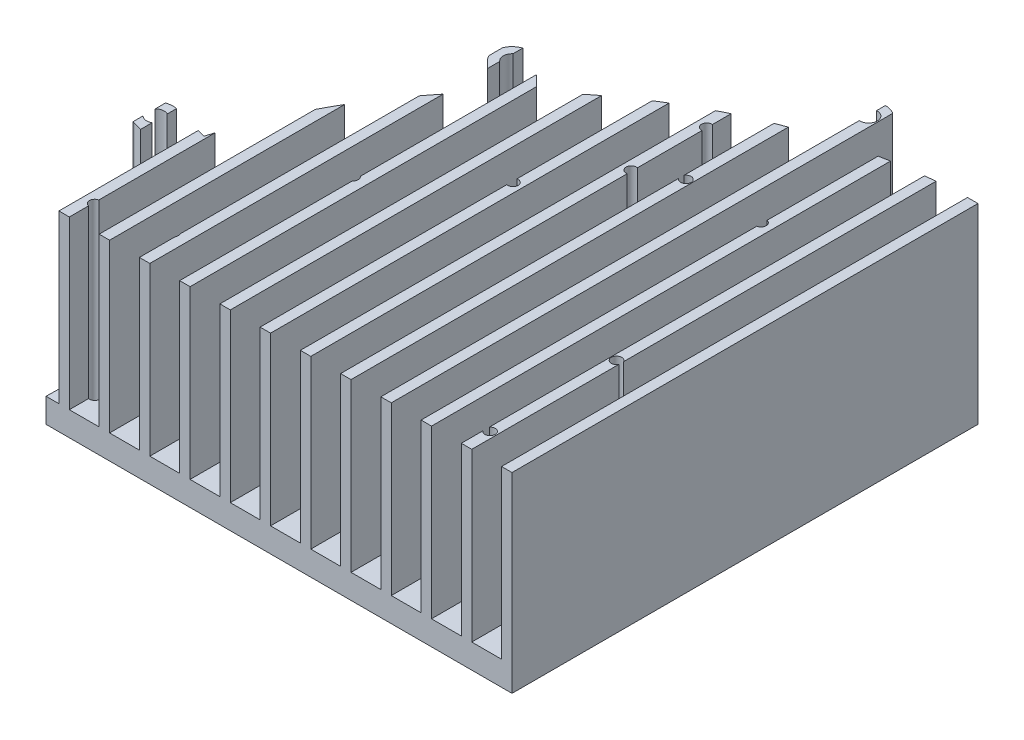
SolidWorks part; units mm, degrees
ref_plane "Ön Düzlem" through (0, 0, 0) normal (0, 0, 1) x (1, 0, 0)
ref_plane "Üst Düzlem" through (0, 0, 0) normal (0, 1, 0) x (1, 0, 0)
ref_plane "Sağ Düzlem" through (0, 0, 0) normal (1, 0, 0) x (0, 0, -1)
sketch "Sketch1" plane through (0, 0, 0) normal (0, 0, 1) x (1, 0, 0)
  line L0 (11.5714, 7) -> (11.5714, 55)
  line L1 (0, 0) -> (165, 0)
  line L2 (0, 0) -> (0, 7)
  line L3 (3, 7) -> (11.5714, 7)
  line L4 (165, 0) -> (165, 10)
  line L6 (0, 7) -> (0, 55)
  line L7 (0, 55) -> (3, 55)
  line L8 (3, 7) -> (3, 55)
  line L10 (14.5714, 7) -> (14.5714, 55)
  line L11 (11.5714, 55) -> (14.5714, 55)
  line L12 (23.1429, 7) -> (23.1429, 55)
  line L14 (26.1429, 7) -> (26.1429, 55)
  line L15 (23.1429, 55) -> (26.1429, 55)
  line L16 (34.7143, 7) -> (34.7143, 55)
  line L18 (37.7143, 7) -> (37.7143, 55)
  line L19 (34.7143, 55) -> (37.7143, 55)
  line L20 (46.2857, 7) -> (46.2857, 55)
  line L22 (49.2857, 7) -> (49.2857, 55)
  line L23 (46.2857, 55) -> (49.2857, 55)
  line L24 (57.8571, 7) -> (57.8571, 55)
  line L26 (60.8571, 7) -> (60.8571, 55)
  line L27 (57.8571, 55) -> (60.8571, 55)
  line L28 (69.4286, 7) -> (69.4286, 55)
  line L30 (72.4286, 7) -> (72.4286, 55)
  line L31 (69.4286, 55) -> (72.4286, 55)
  line L32 (81, 7) -> (81, 55)
  line L34 (84, 7) -> (84, 55)
  line L35 (81, 55) -> (84, 55)
  line L36 (92.5714, 7) -> (92.5714, 55)
  line L38 (95.5714, 7) -> (95.5714, 55)
  line L39 (92.5714, 55) -> (95.5714, 55)
  line L40 (104.1429, 7) -> (104.1429, 55)
  line L42 (107.1429, 7) -> (107.1429, 55)
  line L43 (104.1429, 55) -> (107.1429, 55)
  line L44 (115.7143, 7) -> (115.7143, 55)
  line L46 (118.7143, 7) -> (118.7143, 55)
  line L47 (115.7143, 55) -> (118.7143, 55)
  line L48 (127.2857, 7) -> (127.2857, 55)
  line L50 (130.2857, 7) -> (130.2857, 55)
  line L51 (127.2857, 55) -> (130.2857, 55)
  line L52 (138.8571, 7) -> (138.8571, 55)
  line L54 (141.8571, 7) -> (141.8571, 55)
  line L55 (138.8571, 55) -> (141.8571, 55)
  line L56 (150.4286, 7) -> (150.4286, 55)
  line L58 (153.4286, 7) -> (153.4286, 55)
  line L59 (150.4286, 55) -> (153.4286, 55)
  line L60 (162, 7) -> (162, 55)
  line L62 (165, 7) -> (165, 55)
  line L63 (162, 55) -> (165, 55)
  line L78 (14.5714, 7) -> (23.1429, 7)
  line L79 (26.1429, 7) -> (34.7143, 7)
  line L80 (37.7143, 7) -> (46.2857, 7)
  line L81 (49.2857, 7) -> (57.8571, 7)
  line L82 (60.8571, 7) -> (69.4286, 7)
  line L83 (72.4286, 7) -> (81, 7)
  line L84 (84, 7) -> (92.5714, 7)
  line L85 (95.5714, 7) -> (104.1429, 7)
  line L86 (107.1429, 7) -> (115.7143, 7)
  line L87 (118.7143, 7) -> (127.2857, 7)
  line L88 (130.2857, 7) -> (138.8571, 7)
  line L89 (141.8571, 7) -> (150.4286, 7)
  line L90 (153.4286, 7) -> (162, 7)
  dimension "D1" = 165
  dimension "D2" = 7
  dimension "D3" = 48
  dimension "D4" = 3
  dimension "D5" = 15
extrude "Boss-Extrude1" add sketch "Sketch1" along normal blind 1000 contours L90 L58 L59 L56 L89 L54 L55 L52 L88 L50 L51 L48 L87 L46 L47 L44 L86 L42 L43 L40 L85 L38 L39 L36 L84 L34 L35 L32 L83 L30 L31 L28 L82 L26 L27 L24 L81 L22 L23 L20 L80 L18 L19 L16 L79 L14 L15 L12 L78 L10 L11 region at (82.5, 21.4186, 0)
sketch "Sketch3" plane through (0, 0, 0) normal (0, -1, 0) x (1, 0, 0)
  line L1 (165, 1000) -> (165, 0) construction
  line L3 (0, 0) -> (165, 0) construction
  line L23 (165, 200) -> (0, 200) construction
  line L24 (0, 1000) -> (0, 0) construction
  line L25 (165, 334) -> (0, 334) construction
  line L26 (165, 334) -> (118.1105, 159.006) construction
  line L27 (165, 334) -> (36.8955, 205.8955) construction
  line L28 (165, 334) -> (-9.994, 287.1105) construction
  line L29 (165, 334) -> (118.1105, 159.006) construction
  line L30 (165, 334) -> (127.4712, 193.9408) construction
  line L31 (165, 334) -> (127.4712, 193.9408) construction
  line L32 (132.3009, 192.6467) -> (135.172, 203.362)
  line L33 (122.6416, 195.2349) -> (125.5128, 205.9502)
  line L34 (66.0051, 227.934) -> (73.8492, 235.7781)
  line L35 (58.934, 235.0051) -> (66.7781, 242.8492)
  line L36 (26.2349, 291.6416) -> (36.9502, 294.5128)
  line L37 (23.6467, 301.3009) -> (34.362, 304.172)
  line L38 (165, 334) -> (135.172, 203.362) construction
  line L39 (165, 200) -> (165, 334)
  line L40 (165, 334) -> (31, 334)
  line L41 (165, 184) -> (0, 184) construction
  line L42 (165, 344) -> (0, 344) construction
  line L43 (0, 184) -> (0, 344) construction
  line L44 (165, 200) -> (165, 184) construction
  line L45 (165, 344) -> (165, 334) construction
  arc A1 (165, 200) -> (31, 334) centre (165, 334) cw construction
  circle A7 centre (117, 236) radius 1.5
  circle A8 centre (106.834, 241.544) radius 1.5
  arc A10 (165, 184) -> (15, 334) centre (165, 334) cw construction
  arc A11 (165, 189) -> (20, 334) centre (165, 334) cw construction
  circle A12 centre (127.4712, 193.9408) radius 2.5
  circle A13 centre (62.4695, 231.4695) radius 2.5
  circle A14 centre (24.9408, 296.4712) radius 2.5
  arc A15 (122.6646, 195.3179) -> (132.3225, 192.7301) centre (127.4712, 193.9408) ccw
  arc A16 (58.9955, 235.0655) -> (66.0655, 227.9955) centre (62.4695, 231.4695) ccw
  arc A17 (23.7301, 301.3225) -> (26.3179, 291.6646) centre (24.9408, 296.4712) ccw
  arc A18 (165, 200) -> (135.172, 203.362) centre (165, 334) cw
  arc A19 (125.5128, 205.9502) -> (73.8492, 235.7781) centre (165, 334) cw
  arc A20 (66.7781, 242.8492) -> (36.9502, 294.5128) centre (165, 334) cw
  arc A21 (34.362, 304.172) -> (31, 334) centre (165, 334) cw
  circle A22 centre (159, 206) radius 1.5
  circle A23 centre (159.945, 224.958) radius 1.5
  circle A24 centre (138.59, 236) radius 1.5
  circle A25 centre (107, 220) radius 1.5
  circle A26 centre (92.864, 261.61) radius 1.5
  circle A27 centre (74.576, 273.548) radius 1.5
  circle A28 centre (68.48, 283.2) radius 1.5
  circle A29 centre (51, 276) radius 1.5
  circle A30 centre (152.097, 291.028) radius 1.5
  circle A31 centre (133.3, 304.5) radius 1.5
  circle A32 centre (66.702, 306.822) radius 1.5
  circle A33 centre (56.542, 323.078) radius 1.5
  circle A34 centre (38, 327) radius 1.5
  circle A35 centre (124, 325) radius 1.5
  circle A36 centre (158, 321) radius 1.501
  circle A37 centre (151.6, 326.9) radius 1.5
  point P101 (0, 0)
  line M2 (0, 0) -> (165, 0)
  line M3 (165, 0) -> (165, 1000)
  line M4 (165, 1000) -> (0, 1000)
  line M5 (0, 1000) -> (0, 0)
  dimension "D5" = 48
  dimension "D7" = 3
  dimension "D8" = 3
  dimension "D10" = 92.456
  dimension "D20" = 150
  dimension "D21" = 145
  dimension "D22" = 134
  dimension "D23" = 5
  dimension "D26" = 10
  dimension "D32" = 3
  dimension "D35" = 3
  dimension "D38" = 3
  dimension "D41" = 3
  dimension "D11" = 3
  dimension "D44" = 3
  dimension "D47" = 3
  dimension "D50" = 3
  dimension "D53" = 3
  dimension "D56" = 3
  dimension "D61" = 3
  dimension "D62" = 3
  dimension "D65" = 3
  dimension "D68" = 3
  dimension "D69" = 3.002
  dimension "D70" = 3
  dimension "D6" = 98
  dimension "D9" = 58.166
  dimension "D14" = 134
  dimension "D15" = 200
  dimension "D16" = 15
  dimension "D18" = 30
  dimension "D19" = 30
  dimension "D25" = 145
  dimension "D28" = 145
  dimension "D30" = 134
  dimension "D31" = 10
  dimension "D33" = 6
  dimension "D34" = 128
  dimension "D36" = 5.055
  dimension "D37" = 109.042
  dimension "D39" = 26.41
  dimension "D40" = 98
  dimension "D42" = 58
  dimension "D43" = 114
  dimension "D12" = 72.136
  dimension "D13" = 72.39
  dimension "D45" = 60.452
  dimension "D46" = 90.424
  dimension "D48" = 50.8
  dimension "D49" = 96.52
  dimension "D51" = 114
  dimension "D52" = 58
  dimension "D54" = 12.903
  dimension "D55" = 42.972
  dimension "D57" = 29.5
  dimension "D58" = 31.7
  dimension "D59" = 98.298
  dimension "D60" = 27.178
  dimension "D63" = 108.458
  dimension "D64" = 10.922
  dimension "D66" = 7
  dimension "D67" = 127
  dimension "D71" = 41
  dimension "D72" = 9
  dimension "D73" = 7
  dimension "D74" = 13
  dimension "D75" = 13.4
  dimension "D76" = 7.1
  dimension "D17" = 3
  dimension "D24" = 3
  dimension "D27" = 3
  dimension "D29" = 3
extrude "Cut-Extrude3" cut sketch "Sketch3" against normal blind 100 contours L37 A21 L40 A18 L32 A15 L33 A19 L34 A16 L35 A20 L36 A17 M3 M4 M5 M2 region at (80.1233, 0, 521.6582)
extrude "Cut-Extrude4" cut sketch "Sketch3<6>" against normal blind 100 contours A12 | A13 | A14 | A23 | A22 | A24 | A25 | A7 | A8 | A26 | A27 | A29 | A28 | A32 | A34 | A33 | A35 | A31 | A30 | A37 | A36
sketch "Sketch3<6>" plane through (0, 0, 0) normal (0, -1, 0) x (1, 0, 0) same geometry as "Sketch3"
